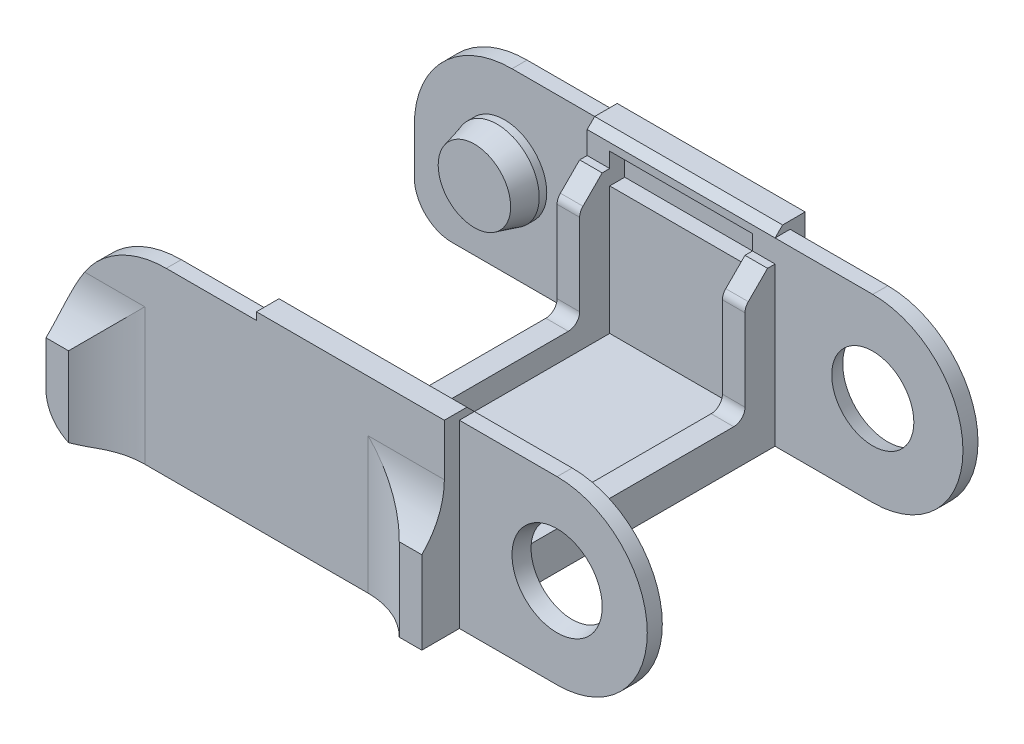
SolidWorks part; units mm, degrees
ref_plane "Front" through (0, 0, 0) normal (0, 0, 1) x (1, 0, 0)
ref_plane "Top" through (0, 0, 0) normal (0, 1, 0) x (1, 0, 0)
ref_plane "Right" through (0, 0, 0) normal (1, 0, 0) x (0, 0, -1)
sketch "Эскиз1" plane through (0, 0, 0) normal (0, 0, 1) x (1, 0, 0)
  line L1 (-38.7795, 23.7195) -> (-13.7795, 23.7195)
  line L2 (-38.7795, 23.7195) -> (-38.7795, -1.2805)
  line L3 (-38.7795, -1.2805) -> (-13.7795, -1.2805)
  line L4 (-13.7795, 23.7195) -> (-13.7795, -1.2805)
  dimension "D1" = 25
  dimension "D2" = 25
extrude "Бобышка-Вытянуть1" add sketch "Эскиз1" along normal blind 4
sketch "Эскиз2" plane through (0, 0, 0) normal (0, 0, -1) x (-1, 0, 0)
  line L0 (38.7795, 22.7195) -> (63.7795, 22.7195)
  line L1 (38.7795, 23.7195) -> (38.7795, -1.2805) construction
  line L3 (63.7795, 22.7195) -> (63.7795, -1.2805)
  line L4 (63.7795, -1.2805) -> (38.7795, -1.2805)
  line L5 (38.7795, -1.2805) -> (38.7795, 22.7195)
  dimension "D1" = 24
  dimension "D2" = 25
extrude "Бобышка-Вытянуть2" add sketch "Эскиз2" against normal blind 2
sketch "Эскиз3" plane through (0, 0, 2) normal (0, 0, 1) x (1, 0, 0)
  line L1 (-38.7795, -1.2805) -> (-63.7795, -1.2805) construction
  line L2 (-63.7795, -1.2805) -> (-63.7795, 22.7195) construction
  circle A0 centre (-51.7795, 10.7195) radius 5.625
  dimension "D2" = 11.25
  dimension "D1" = 12
  dimension "D3" = 12
extrude "Бобышка-Вытянуть3" add sketch "Эскиз3" along normal blind 4
chamfer "Фаска1" distance 3 angle 15 1 edges at (-46.1545, 10.7195, 6) first distance on face at (-46.1545, 10.7195, 6)
sketch "Эскиз4" plane through (0, 0, 6) normal (0, 0, 1) x (1, 0, 0)
  circle A1 centre (-51.7795, 10.7195) radius 13
  circle A4 centre (-51.7795, 10.7195) radius 7.5542
sketch "Эскиз5" plane through (0, 0, 4) normal (0, 0, 1) x (1, 0, 0)
  line L0 (-18.982, 10.7195) -> (-0.7795, 10.7195) construction
  line L1 (-18.982, 22.7195) -> (-0.7795, 22.7195)
  line L2 (-18.982, -1.2805) -> (-0.7795, -1.2805)
  line L3 (-13.7795, -1.2805) -> (-13.7795, 23.7195) construction
  line L4 (-38.7795, -1.2805) -> (-13.7795, -1.2805) construction
  arc A0 (-18.982, 22.7195) -> (-18.982, -1.2805) centre (-18.982, 10.7195) ccw
  arc A1 (-0.7795, -1.2805) -> (-0.7795, 22.7195) centre (-0.7795, 10.7195) ccw
  point P2 (-9.8808, 10.7195)
  dimension "D1" = 13
  dimension "D2" = 12
  dimension "D3" = 12
extrude "Бобышка-Вытянуть4" add sketch "Эскиз5" against normal blind 2
sketch "Эскиз6" plane through (0, 0, 2) normal (0, 0, -1) x (-1, 0, 0)
  circle A0 centre (0.7795, 10.7195) radius 5
  arc A1 (0.7795, 22.7195) -> (0.7795, -1.2805) centre (0.7795, 10.7195) ccw construction
extrude "Вырез-Вытянуть2" cut sketch "Эскиз6" against normal blind 10
sketch "Эскиз8" plane through (0, 0, 4) normal (0, 0, 1) x (1, 0, 0)
  line L5 (-38.7795, 3.7195) -> (-35.7795, 3.7195)
  line L6 (-38.7795, -1.2805) -> (-13.7795, -1.2805)
  line L7 (-38.7795, -1.2805) -> (-38.7795, 3.7195)
  line L9 (-13.7795, -1.2805) -> (-13.7795, 3.7195)
  line L10 (-35.7795, 3.7195) -> (-35.7795, 0.7195)
  line L11 (-35.7795, 0.7195) -> (-16.7795, 0.7195)
  line L12 (-16.7795, 0.7195) -> (-16.7795, 3.7195)
  line L13 (-16.7795, 3.7195) -> (-13.7795, 3.7195)
  line L14 (-13.7795, 22.7195) -> (-13.7795, 23.7195) construction
  dimension "D1" = 3
  dimension "D2" = 3
  dimension "D3" = 2
  dimension "D4" = 5
  dimension "D5" = 5
extrude "Бобышка-Вытянуть6" add sketch "Эскиз8" along normal blind 20
sketch "Эскиз9" plane through (0, 0, 4) normal (0, 0, 1) x (1, 0, 0)
  line L0 (-38.7795, 23.7195) -> (-38.7795, 3.7195) construction
  line L1 (-35.7795, 20.7195) -> (-16.7795, 20.7195)
  line L2 (-35.7795, 20.7195) -> (-35.7795, 17.7195)
  line L3 (-35.7795, 17.7195) -> (-16.7795, 17.7195)
  line L4 (-16.7795, 20.7195) -> (-16.7795, 17.7195)
  line L5 (-13.7795, 22.7195) -> (-13.7795, 23.7195) construction
  line L6 (-13.7795, 23.7195) -> (-38.7795, 23.7195) construction
  dimension "D1" = 3
  dimension "D2" = 3
  dimension "D3" = 3
  dimension "D4" = 6
extrude "Вырез-Вытянуть4" cut sketch "Эскиз9" against normal blind 2
chamfer "Фаска2" distance 1 angle 45 1 edges at (-26.2795, 20.7195, 4)
chamfer "Фаска3" distance 1 angle 75 1 edges at (-5.7795, 10.7195, 2) first distance on face at (-5.7795, 10.7195, 2)
fillet "Скругление1" radius 13 1 edges at (-63.7795, 22.7195, 1)
chamfer "Фаска4" distance 1 angle 45 1 edges at (-26.2795, 23.7195, 4)
sketch "Эскиз11" plane through (0, 3.7195, 0) normal (0, 1, 0) x (1, 0, 0)
  line L0 (-35.7795, -24) -> (-35.7795, -4) construction
  line L1 (-38.7795, -4) -> (-35.7795, -4)
  line L2 (-38.7795, -4) -> (-38.7795, -8)
  line L3 (-38.7795, -8) -> (-35.7795, -8)
  line L4 (-35.7795, -4) -> (-35.7795, -8)
  dimension "D1" = 4
extrude "Бобышка-Вытянуть7" add sketch "Эскиз11" along normal blind 16
pattern_linear "Линейный массив1" count 2 spacing 22 along (1, 0, 0) of "Бобышка-Вытянуть7"
chamfer "Фаска6" distance 3 angle 45 2 edges at (-15.2795, 19.7195, 8) (-37.2795, 19.7195, 8)
fillet "Скругление2" radius 1.5 4 edges at (-15.2795, 3.7195, 8) (-15.2795, 16.7195, 8) (-37.2795, 16.7195, 8) (-37.2795, 3.7195, 8)
sketch "Sketch1" plane through (0, 0, 0) normal (0, 0, -1) x (-1, 0, 0)
  line L0 (63.7795, -1.2805) -> (13.7795, -1.2805) construction
  line L1 (13.7795, 9.7195) -> (16.7795, 9.7195)
  line L2 (13.7795, 9.7195) -> (13.7795, -1.2805)
  line L3 (13.7795, -1.2805) -> (16.7795, -1.2805)
  line L4 (16.7795, 9.7195) -> (16.7795, -1.2805)
  dimension "D1" = 3
  dimension "D2" = 11
extrude "Boss-Extrude1" add sketch "Sketch1" along normal blind 3
fillet "Fillet1" radius 10 2 edges at (-16.7795, 4.2195, 0) (-15.2795, 9.7195, 0)
sketch "Sketch2" plane through (0, 0, 0) normal (0, 0, -1) x (-1, 0, 0)
  line L1 (63.7795, -1.2805) -> (60.7795, -1.2805)
  line L2 (63.7795, -1.2805) -> (63.7795, 9.7195)
  line L3 (63.7795, 9.7195) -> (60.7795, 9.7195)
  line L4 (60.7795, -1.2805) -> (60.7795, 9.7195)
  dimension "D1" = 11
  dimension "D2" = 3
extrude "Boss-Extrude2" add sketch "Sketch2" along normal blind 3
fillet "Fillet2" radius 10 2 edges at (-62.2795, 9.7195, 0) (-60.7795, 4.2195, 0)
fillet "Fillet3" radius 5 1 edges at (-63.7795, -1.2805, -0.5)
mirror "Зеркальное отражение1" about plane through (0, 0, 24) normal (0, 0, -1) of bodies 115 109
